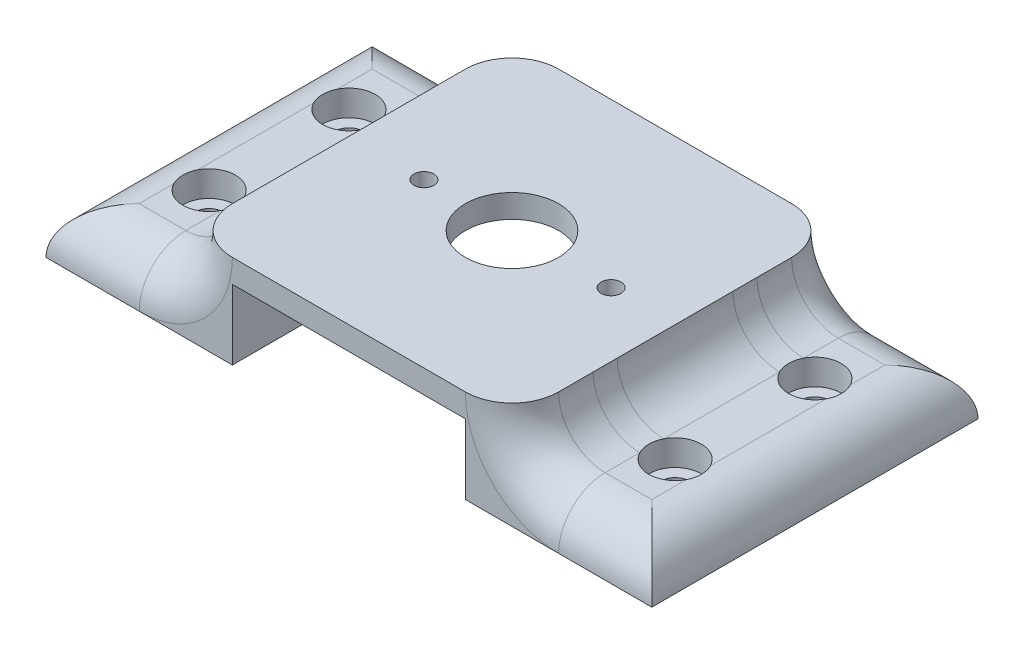
SolidWorks part; units mm, degrees
material "ABS"
ref_plane "Front Plane" through (0, 0, 0) normal (0, 0, 1) x (1, 0, 0)
ref_plane "Top Plane" through (0, 0, 0) normal (0, 1, 0) x (1, 0, 0)
ref_plane "Right Plane" through (0, 0, 0) normal (1, 0, 0) x (0, 0, -1)
sketch "Sketch1" plane through (0, 0, 0) normal (0, 0, 1) x (1, 0, 0)
  line L0 (0, 0) -> (0, 12.7) construction
  line L1 (0, 0) -> (-41.275, 0) construction
  line L2 (0, 0) -> (41.275, 0) construction
  line L3 (-41.275, 0) -> (-41.275, 6.35)
  line L4 (-41.275, 0) -> (-15.875, 0)
  line L5 (41.275, 0) -> (41.275, 6.35)
  line L6 (41.275, 0) -> (15.875, 0)
  line L7 (15.875, 9.525) -> (-15.875, 9.525)
  line L8 (15.875, 6.35) -> (15.875, 9.525)
  line L9 (-22.225, 12.7) -> (-22.225, 6.35)
  line L10 (-15.875, 0) -> (-15.875, 6.35)
  line L11 (41.275, 6.35) -> (22.225, 6.35)
  line L12 (-41.275, 6.35) -> (-22.225, 6.35)
  line L13 (22.225, 12.7) -> (22.225, 6.35)
  line L14 (15.875, 6.35) -> (15.875, 0)
  line L15 (-15.875, 6.35) -> (-15.875, 9.525)
  line L19 (22.225, 12.7) -> (-22.225, 12.7)
  dimension "D2" = 41.275
  dimension "D3" = 41.275
  dimension "D4" = 6.35
  dimension "D5" = 25.4
  dimension "D6" = 6.35
  dimension "D7" = 25.4
  dimension "D8" = 12.7
  dimension "D9" = 3.175
  dimension "D10" = 19.05
  dimension "D12" = 19.05
  dimension "D13" = 6.35
  dimension "D14" = 6.35
extrude "Boss-Extrude1" add sketch "Sketch1" along normal blind 44.45
sketch "Sketch2" plane through (0, 12.7, 0) normal (0, 1, 0) x (1, 0, 0)
  line L0 (0, 0) -> (0, -44.45) construction
  line L1 (22.225, -44.45) -> (-22.225, -44.45) construction
  circle A0 centre (0, -22.225) radius 6.35
extrude "Cut-Extrude1" cut sketch "Sketch2" against normal blind 44.45
hole_wizard "CBORE for #6 Socket Head Cap Screw1" positions "3DSketch1" profile "Sketch3" counterbore size "#6" standard "Ansi Inch" end condition through all
sketch3d "3DSketch1"
  line L0 (-31.75, 6.35, 0) -> (-31.75, 6.35, 44.45) construction
  line L1 (-22.225, 6.35, 0) -> (-41.275, 6.35, 0) construction
  line L2 (-22.225, 6.35, 44.45) -> (-41.275, 6.35, 44.45) construction
  line L3 (31.75, 6.35, 0) -> (31.75, 6.35, 44.45) construction
  line L4 (41.275, 6.35, 0) -> (22.225, 6.35, 0) construction
  line L5 (41.275, 6.35, 44.45) -> (22.225, 6.35, 44.45) construction
  line L6 (-41.275, 6.35, 12.7) -> (-22.225, 6.35, 12.7) construction
  line L7 (-41.275, 6.35, 44.45) -> (-41.275, 6.35, 0) construction
  line L8 (-22.225, 6.35, 44.45) -> (-22.225, 6.35, 0) construction
  line L9 (-41.275, 6.35, 31.75) -> (-22.225, 6.35, 31.75) construction
  line L10 (22.225, 6.35, 12.7) -> (41.275, 6.35, 12.7) construction
  line L11 (22.225, 6.35, 44.45) -> (22.225, 6.35, 0) construction
  line L12 (41.275, 6.35, 44.45) -> (41.275, 6.35, 0) construction
  line L13 (22.225, 6.35, 31.75) -> (41.275, 6.35, 31.75) construction
  point P0 (31.75, 6.35, 31.75)
  point P2 (31.75, 6.35, 12.7)
  point P4 (-31.75, 6.35, 31.75)
  point P6 (-31.75, 6.35, 12.7)
  dimension "D1" = 12.7
  dimension "D2" = 12.7
  dimension "D3" = 12.7
  dimension "D4" = 12.7
sketch "Sketch3" plane through (31.75, 6.35, 31.75) normal (1, 0, 0) x (0, 0, 1)
  line L0 (0, 0) -> (0, 6.35)
  line L1 (0, 6.35) -> (1.8987, 6.35)
  line L3 (1.8987, 6.35) -> (1.8986, 3.5052)
  line L4 (1.8986, 3.5052) -> (3.5725, 3.5052)
  line L5 (3.5725, 3.5052) -> (3.5725, 0)
  line L7 (3.5725, 0) -> (0, 0)
  line L11 (0, -6.35) -> (0, 107.95) construction
  dimension "Thru Hole Dia." = 3.7973
  dimension "Thru Hole Depth" = 6.35
  dimension "C'Bore Dia." = 7.145
  dimension "C'Bore Depth" = 3.5052
hole_wizard "#6-32 Tapped Hole1" positions "3DSketch2" profile "Sketch4" tap size "#6-32" standard "Ansi Inch"
sketch3d "3DSketch2"
  line L0 (0, 12.7, 22.225) -> (-12, 12.7, 22.225) construction
  line L1 (0, 9.525, 22.225) -> (0, 12.7, 22.225) construction
  line L2 (0, 12.7, 22.225) -> (13.5001, 12.7, 22.225) construction
  point P0 (-12, 12.7, 22.225)
  point P2 (13.5001, 12.7, 22.225)
  dimension "D1" = 13.5001
  dimension "D2" = 12
sketch "Sketch4" plane through (-12, 12.7, 22.225) normal (1, 0, 0) x (0, 0, 1)
  line L0 (0, 0) -> (0, 13.7667)
  line L1 (0, 13.7667) -> (1.3525, 12.954)
  line L2 (1.3525, 12.954) -> (1.3525, 0)
  line L5 (1.3525, 0) -> (0, 0)
  line L10 (0, 13.7667) -> (-1.3525, 12.954) construction
  line L11 (0, -6.35) -> (0, 107.95) construction
  dimension "Tap Drill Dia." = 2.7051
  dimension "Tap Drill Depth" = 12.954
  dimension "Drill Angle" = 118
cosmetic thread "Hole Thread1" parameters "D1"=8.89, "D2"=3.5052
cosmetic thread "Hole Thread2" parameters "D1"=8.89, "D2"=3.5052
fillet "Fillet1" radius 6.35 8 edges at (-22.225, 6.35, 22.225) (22.225, 6.35, 22.225) (-31.75, 6.35, 0) (31.75, 6.35, 0) (-31.75, 6.35, 44.45) (31.75, 6.35, 44.45) (41.275, 6.35, 22.225) (-41.275, 6.35, 22.225)
